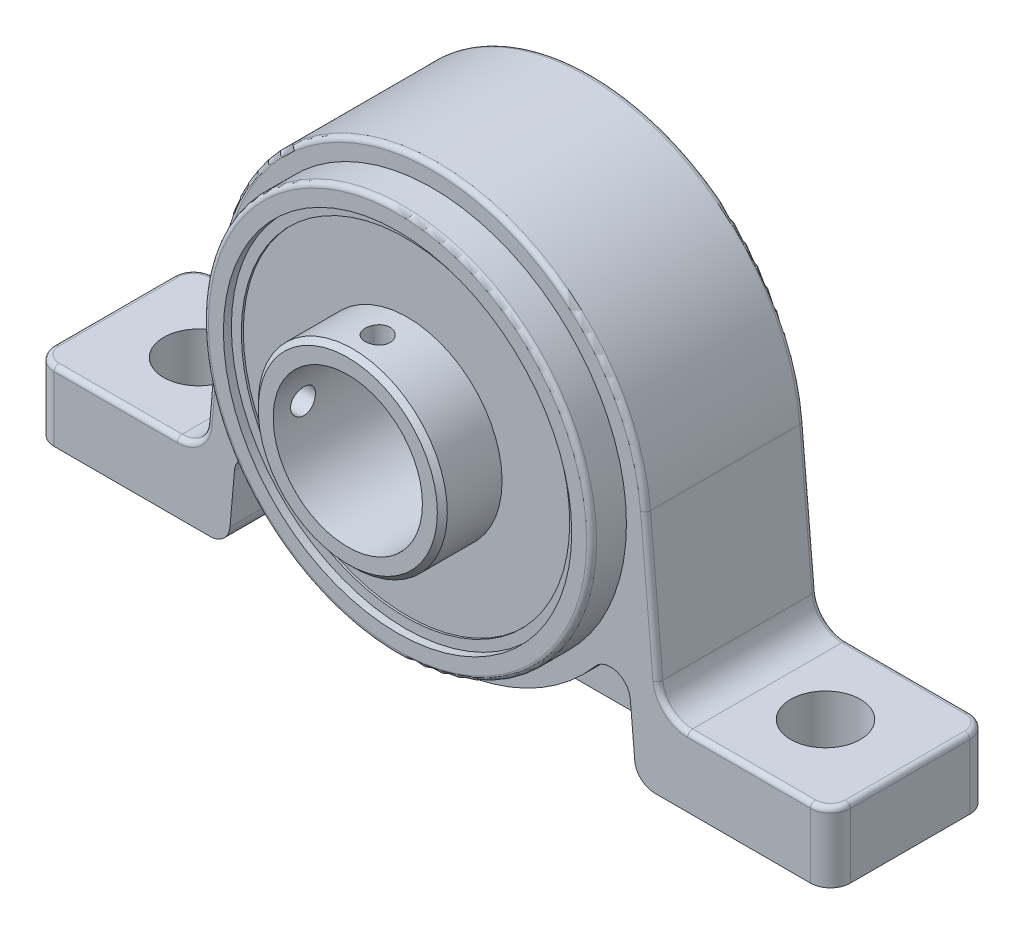
SolidWorks part; units mm, degrees
ref_plane "Front Plane" through (0, 0, 0) normal (0, 0, 1) x (1, 0, 0)
ref_plane "Top Plane" through (0, 0, 0) normal (0, 1, 0) x (1, 0, 0)
ref_plane "Right Plane" through (0, 0, 0) normal (1, 0, 0) x (0, 0, -1)
sketch "Sketch1" plane through (0, 0, 0) normal (0, 0, 1) x (1, 0, 0)
  line L0 (0, 0) -> (-11670.9506, 0) construction
  line L1 (0, 0) -> (0, 11670.9506) construction
  line L2 (-40, 0) -> (-40, 7)
  line L3 (-40, 7) -> (-25.6434, 7)
  line L4 (-40, 0) -> (-22.3281, 0)
  line L5 (-20.3357, 1.8257) -> (-19.888, 6.9429)
  line L6 (-22.6549, 9.7385) -> (-21.4182, 23.8738)
  line L7 (40, -4.905) -> (-40, -4.905) construction
  line L8 (8.5, -4.905) -> (8.5, -1.8884) construction
  line L9 (-8.5, -4.905) -> (-8.5, -1.8884) construction
  line L10 (0, 0) -> (11670.9506, 0) construction
  line L11 (22.6549, 9.7385) -> (21.4182, 23.8738)
  line L12 (20.3357, 1.8257) -> (19.888, 6.9429)
  line L13 (40, 0) -> (22.3281, 0)
  line L14 (40, 7) -> (25.6434, 7)
  line L15 (40, 0) -> (40, 7)
  circle A0 centre (0, 22) radius 7.5
  arc A1 (-16.3726, 8.0648) -> (16.3726, 8.0648) centre (0, 22) ccw
  circle A2 centre (0, 22) radius 19.5
  arc A3 (-22.6549, 9.7385) -> (-25.6434, 7) centre (-25.6434, 10) cw
  arc A4 (-20.3357, 1.8257) -> (-22.3281, 0) centre (-22.3281, 2) cw
  arc A5 (-16.3726, 8.0648) -> (-19.888, 6.9429) centre (-17.8956, 6.7685) ccw
  circle A6 centre (0, 22) radius 21.5 construction
  circle A7 centre (0, 22) radius 9.5
  circle A8 centre (0, 22) radius 17.5
  circle A9 centre (0, 22) radius 16.5
  arc A10 (16.3726, 8.0648) -> (19.888, 6.9429) centre (17.8956, 6.7685) cw
  arc A11 (20.3357, 1.8257) -> (22.3281, 0) centre (22.3281, 2) ccw
  arc A12 (22.6549, 9.7385) -> (25.6434, 7) centre (25.6434, 10) ccw
  arc A13 (21.4182, 23.8738) -> (-21.4182, 23.8738) centre (0, 22) ccw
  point P11 (-13.991, 0)
  point P18 (0, -4.905)
  point P22 (0, 0)
  point P25 (-15, 5)
  point P26 (0, 0)
  point P27 (-16.659, 5)
  point P28 (-14.4495, 0)
  point P33 (-20.4954, 0)
  point P34 (14.3446, 20.3856)
  point P57 (20.4954, 0)
  dimension "D1" = 15
  dimension "D3" = 43
  dimension "D10" = 3
  dimension "D11" = 2
  dimension "D12" = 2
  dimension "D2" = 22
  dimension "D4" = 80
  dimension "D6" = 7
  dimension "D7" = 3
  dimension "D9" = 85
  dimension "D8" = 2
  dimension "D13" = 2
  dimension "D14" = 2
  dimension "D15" = 1
extrude "B" add sketch "Sketch1" along normal blind 16 contours L11 A13 L6 A3 L3 L2 L4 A4 L5 A5 A1 A10 L12 A11 L13 L15 L14 A12 A2 region at (-39.0894, 3.5, 0)
extrude "B1S" add sketch "Sketch1<3>" along normal blind 16.5 from offset 3 contours A2 A8 region at (-18.9485, 22, 0)
sketch "Sketch1<3>" plane through (0, 0, 0) normal (0, 0, 1) x (1, 0, 0) same geometry as "Sketch1"
extrude "Boss-Extrude3" add sketch "Sketch1<4>" along normal blind 15.5 from offset 3.2 contours A8 A9 region at (-17.005, 22, 0)
sketch "Sketch1<4>" plane through (0, 0, 0) normal (0, 0, 1) x (1, 0, 0) same geometry as "Sketch1"
extrude "Boss-Extrude4" add sketch "Sketch1<6>" along normal blind 15 from offset 3.5 contours A9 A7 region at (-16.0333, 22, 0)
sketch "Sketch1<6>" plane through (0, 0, 0) normal (0, 0, 1) x (1, 0, 0) same geometry as "Sketch1"
extrude "A" add sketch "Sketch1<7>" along normal blind 21.5 from offset 3 contours A7 A0 region at (-9.2313, 22, 0)
sketch "Sketch1<7>" plane through (0, 0, 0) normal (0, 0, 1) x (1, 0, 0) same geometry as "Sketch1"
ref_plane "Plane1" through (0, 0, 8) normal (0, 0, 1) x (1, 0, 0)
sketch "Sketch2" plane through (0, 0, 8) normal (0, 0, 1) x (1, 0, 0)
  line L0 (22.3281, 0) -> (-22.3281, 0)
  line L1 (-22.3281, 0) -> (-22.3281, 5.5)
  line L2 (-22.3281, 5.5) -> (22.3281, 5.5)
  line L3 (22.3281, 5.5) -> (22.3281, 0)
  dimension "D1" = 44.6562
  dimension "D2" = 5.5
extrude "Boss-Extrude6" add sketch "Sketch2" along normal mid plane 4
sketch "Sketch3" plane through (0, 0, 0) normal (1, 0, 0) x (0, 0, -1)
  line L0 (-18, 22) -> (49982, 22) construction
  line L1 (-24.5, 31.5) -> (-24.5, 12.5) construction
  line L2 (-21.5, 22) -> (-21.5, -49978) construction
  line L3 (-18.5, 31.5) -> (-24.5, 31.5) construction
  circle A0 centre (-21.5, 22) radius 1.25
  point P4 (-24.5, 22)
  point P9 (-21.5, 31.5)
  point P12 (-16, 16)
  dimension "D1" = 2.5
extrude "Cut-Extrude1" cut sketch "Sketch3" against normal up to next
pattern_circular "CirPattern1" count 2 over 90 about axis through (0, 22, 24.5) along (0, 0, -1) of "Cut-Extrude1"
fillet "Fillet1" radius 2 4 edges at (-40, 3.5, 0) (-40, 3.5, 16) (40, 3.5, 0) (40, 3.5, 16)
fillet "Fillet2" radius 0.5 21 edges at (22.0365, 16.8062, 16) (23.6167, 7.7882, 16) (31.8217, 7, 16) (39.4142, 7, 15.4142) (40, 7, 8) (39.4142, 7, 0.5858) (31.8217, 7, 0) (23.6167, 7.7882, 0) (22.0365, 16.8062, 0) (0, 43.5, 0) (-22.0365, 16.8062, 0) (-23.6167, 7.7882, 0) (-31.8217, 7, 0) (-39.4142, 7, 0.5858) (-40, 7, 8) (-39.4142, 7, 15.4142) (-31.8217, 7, 16) (-23.6167, 7.7882, 16) (-22.0365, 16.8062, 16) (0, 43.5, 16) (19.5, 22, 19.5)
fillet "Fillet3" radius 1 1 edges at (19.5, 22, 0)
chamfer "Chamfer1" distance 0.5 angle 45 1 edges at (9.5, 22, 24.5)
sketch "Sketch4" plane through (0, 7, 0) normal (0, 1, 0) x (1, 0, 0)
  line L0 (40, -8) -> (-40, -8) construction
  line L1 (40, -2) -> (40, -14) construction
  line L2 (-40, -14) -> (-40, -2) construction
  line L3 (-40, -8) -> (0, 0) construction
  line L4 (0, 0) -> (0, -24) construction
  line L5 (9.5, -24) -> (-9.5, -24) construction
  circle A0 centre (31.5, -8) radius 3.5
  circle A1 centre (-31.5, -8) radius 3.5
  dimension "D1" = 7
  dimension "D2" = 63
extrude "J" cut sketch "Sketch4" against normal through all
equation "\"D1@Boss-Extrude3\"= \"D1@B1S\" - 1"
equation "\"D1@Boss-Extrude4\"= \"D1@Boss-Extrude3\" - 0.5"
equation "\"D1@A\"=\"D1@B1S\" + 5"
equation "\"B\"= \"D1@B\""
equation "\"A\"= \"D1@B1S\""
equation "\"Bore side\"= \"D1@Sketch1\""
equation "\"H2\"= \"D3@Sketch1\""
equation "\"H\"= \"D2@Sketch1\""
equation "\"L\"= \"D4@Sketch1\""
equation "\"T\"= \"D6@Sketch1\""
equation "\"Hold\"= \"D1@Sketch4\""
